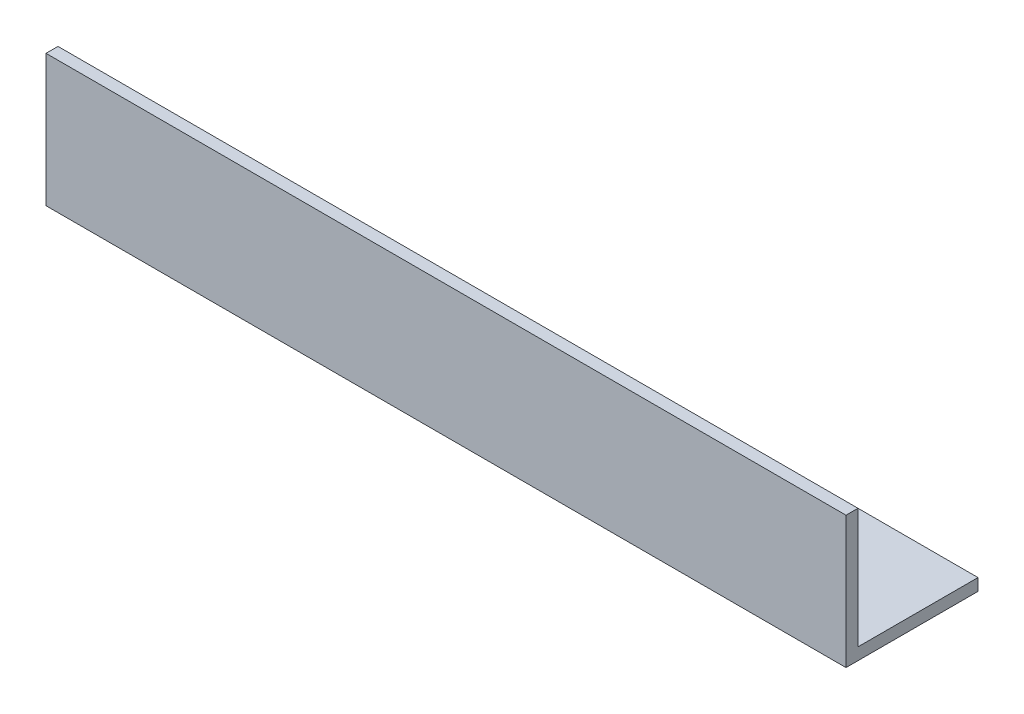
SolidWorks part; units mm, degrees
ref_plane "Спереди" through (0, 0, 0) normal (0, 0, 1) x (1, 0, 0)
ref_plane "Сверху" through (0, 0, 0) normal (0, 1, 0) x (1, 0, 0)
ref_plane "Справа" through (0, 0, 0) normal (1, 0, 0) x (0, 0, -1)
sketch "Эскиз1" plane through (0, 0, 0) normal (1, 0, 0) x (0, 0, -1)
  line L0 (0, 33) -> (0, 0)
  line L1 (0, 0) -> (33, 0)
extrude "Вытянуть-Тонкостенный1" add sketch "Эскиз1" along normal blind 200 thin thin type one direction reverse wall 3
